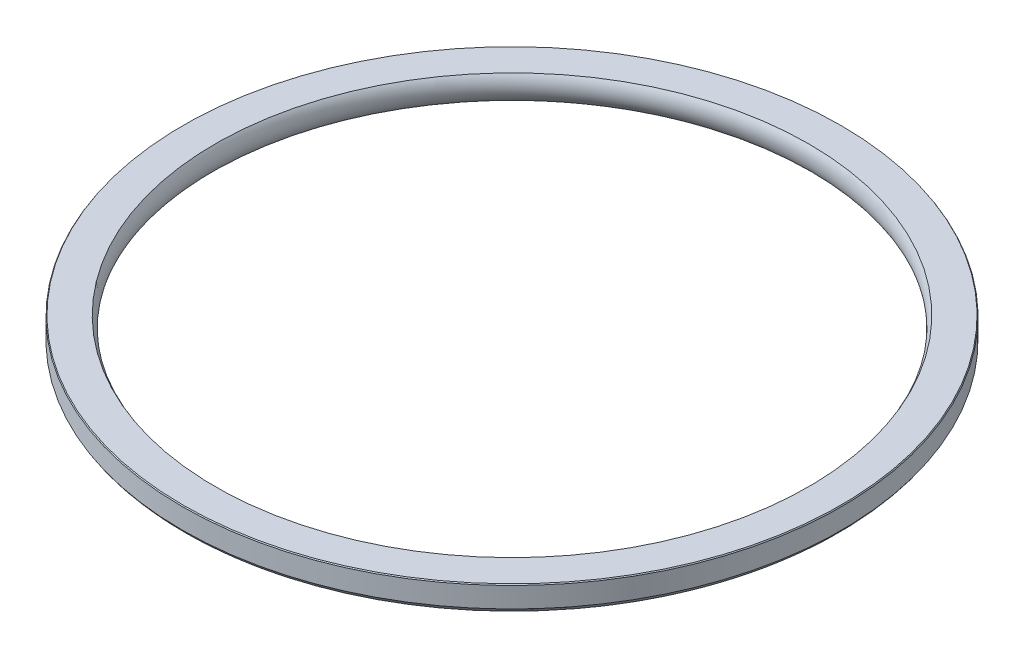
SolidWorks part; units mm, degrees
material "NBR"
ref_plane "Piano frontale" through (0, 0, 0) normal (0, 0, 1) x (1, 0, 0)
ref_plane "Piano superiore" through (0, 0, 0) normal (0, 1, 0) x (1, 0, 0)
ref_plane "Piano destro" through (0, 0, 0) normal (1, 0, 0) x (0, 0, -1)
sketch "Schizzo1" plane through (0, 0, 0) normal (0, 0, 1) x (1, 0, 0)
  line L0 (-14.24, 0) -> (0, 0) construction
  line L1 (0, 0) -> (0, 8.8166) construction
  line L2 (-15, 0.51) -> (-13.5106, 0.51)
  line L3 (-15, -0.4631) -> (-15, 0.4631)
  circle A0 centre (-14.24, 0) radius 0.89
  point P9 (0, 0)
  dimension "D1" = 1.78
  dimension "D2" = 28.48
  dimension "D3" = 30
  dimension "D4" = 0.51
revolve "Rivoluzione1" add sketch "Schizzo1" angle 360 about L1 region at (-14.2072, -0.1282, 0)
